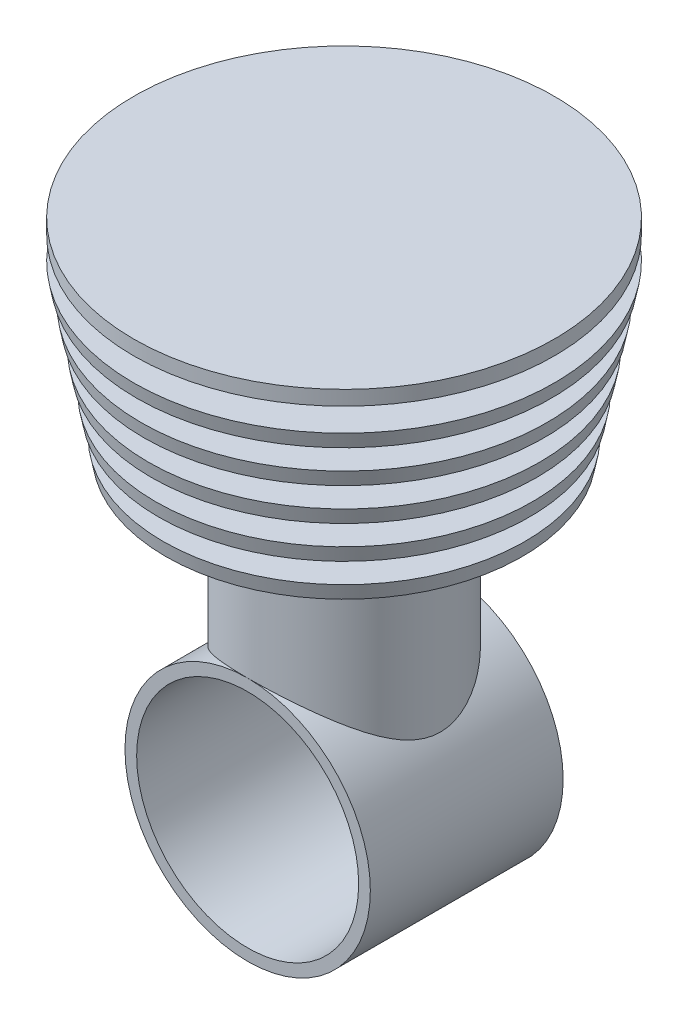
SolidWorks part; units mm, degrees
ref_plane "Plan de face" through (0, 0, 0) normal (0, 0, 1) x (1, 0, 0)
ref_plane "Plan de dessus" through (0, 0, 0) normal (0, 1, 0) x (1, 0, 0)
ref_plane "Plan de droite" through (0, 0, 0) normal (1, 0, 0) x (0, 0, -1)
sketch "Esquisse1" plane through (0, 0, 0) normal (1, 0, 0) x (0, 0, -1)
  line L0 (0, 0) -> (0, -210) construction
  line L1 (-165, -20) -> (165, -20)
  line L2 (-165, -20) -> (-165, 0)
  line L3 (-165, 0) -> (165, 0)
  line L4 (165, -20) -> (165, 0)
  line L5 (0, -210) -> (115.9275, -210) construction
  dimension "D1" = 330
  dimension "D2" = 20
  dimension "D3" = 210
  dimension "D4" = 20
  dimension "D5" = 0
  dimension "D6" = 115.9275
revolve "Révolution3" add sketch "Esquisse1" angle 360 about L5
sketch "Esquisse2" plane through (0, 0, 0) normal (1, 0, 0) x (0, 0, -1)
  line L0 (-165, 0) -> (-165, 250)
  line L1 (-165, 250) -> (-360, 250)
  line L2 (-360, 250) -> (-360, 275)
  line L3 (-360, 275) -> (-165, 275)
  line L4 (-165, 275) -> (-165, 315)
  line L5 (-165, 315) -> (-360, 315)
  line L6 (-360, 315) -> (-360, 340)
  line L7 (-360, 340) -> (-165, 340)
  line L8 (-165, 340) -> (-165, 380)
  line L9 (-165, 380) -> (-360, 380)
  line L10 (-360, 380) -> (-360, 405)
  line L11 (-360, 405) -> (-235, 405)
  line L12 (-235, 405) -> (-235, 445)
  line L13 (-235, 445) -> (-360, 445)
  line L14 (-360, 445) -> (-360, 470)
  line L15 (-360, 470) -> (-235, 470)
  line L16 (-235, 470) -> (-235, 510)
  line L17 (-235, 510) -> (-360, 510)
  line L18 (-360, 510) -> (-360, 535)
  line L19 (-360, 535) -> (-235, 535)
  line L20 (-235, 535) -> (-235, 575)
  line L21 (-235, 575) -> (-360, 575)
  line L22 (-360, 575) -> (-360, 600)
  line L23 (-360, 600) -> (0, 600)
  line L24 (0, 600) -> (0, 560)
  line L25 (0, 560) -> (-135, 560)
  line L26 (-135, 560) -> (-135, 0)
  line L27 (165, 0) -> (-165, 0) construction
  line L28 (-135, 0) -> (-165, 0)
  line L29 (0, 560) -> (0, 0) construction
  dimension "D1" = 360
  dimension "D2" = 40
  dimension "D3" = 250
  dimension "D4" = 30
  dimension "D5" = 25
  dimension "D6" = 25
  dimension "D7" = 25
  dimension "D8" = 25
  dimension "D9" = 25
  dimension "D10" = 25
  dimension "D11" = 100
  dimension "D12" = 600
  dimension "D13" = 135
revolve "Révolution4" add sketch "Esquisse2" angle 360 about L29
sketch "Esquisse3" plane through (0, 0, 0) normal (1, 0, 0) x (0, 0, -1)
  line L0 (0, 600) -> (0, 113.7018) construction
  line L1 (360, 600) -> (-360, 600) construction
  line L2 (-305, 250) -> (-360, 535)
  line L3 (-360, 250) -> (360, 250) construction
  line L4 (-360, 535) -> (-360, 600)
  line L5 (-360, 600) -> (-416.8209, 600)
  line L6 (-416.8209, 600) -> (-416.8209, 250)
  line L7 (-416.8209, 250) -> (-305, 250)
  line L8 (-165, 250) -> (-165, 0) construction
  dimension "D1" = 140
revolve "Enlèvement de matière-Révolution1" cut sketch "Esquisse3" angle 360 about L0
sketch "Esquisse5" plane through (0, 0, 0) normal (0, 1, 0) x (1, 0, 0)
  circle A0 centre (0, 0) radius 165 construction
  circle A1 centre (0, 0) radius 135 construction
  circle A2 centre (0, 0) radius 165
  circle A3 centre (0, 0) radius 135
extrude "Boss.-Extru.1" add sketch "Esquisse5" against normal up to body separate body
sketch "Esquisse6" plane through (0, 0, 0) normal (0, 1, 0) x (1, 0, 0)
  circle A0 centre (0, 0) radius 135 construction
  circle A1 centre (0, 0) radius 135
extrude "Enlèv. mat.-Extru.1" cut sketch "Esquisse6" against normal up to surface (20 mm away)
